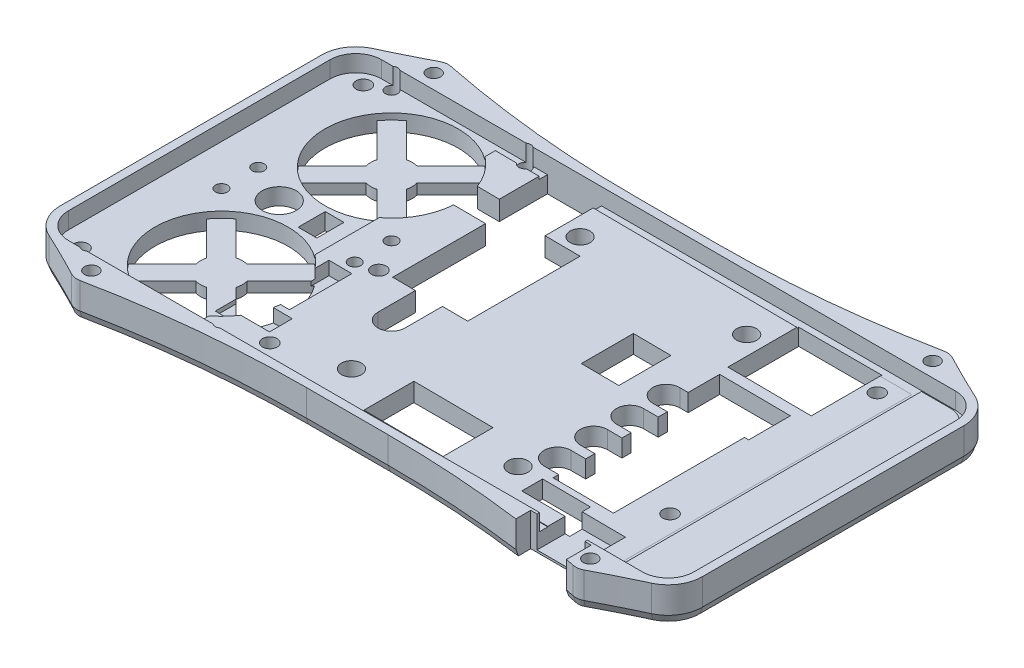
SolidWorks part; units mm, degrees
ref_plane "前视基准面" through (0, 0, 0) normal (0, 0, 1) x (1, 0, 0)
ref_plane "上视基准面" through (0, 0, 0) normal (0, 1, 0) x (1, 0, 0)
ref_plane "右视基准面" through (0, 0, 0) normal (1, 0, 0) x (0, 0, -1)
sketch "草图1" plane through (0, 0, 0) normal (0, 1, 0) x (1, 0, 0)
  line L0 (6, 0.2) -> (143.8, 0.2)
  line L1 (6, 0) -> (143.8, 0) construction
  line L2 (0, -6) -> (0, -68.8) construction
  line L3 (6, -74.8) -> (143.8, -74.8) construction
  line L4 (149.8, -6) -> (149.8, -68.8) construction
  line L5 (150, -6) -> (150, -68.8)
  line L6 (6, -75) -> (143.8, -75)
  line L7 (-0.2, -6) -> (-0.2, -68.8)
  arc A0 (143.8, 0) -> (149.8, -6) centre (143.8, -6) cw construction
  arc A1 (143.8, -74.8) -> (149.8, -68.8) centre (143.8, -68.8) ccw construction
  arc A2 (0, -68.8) -> (6, -74.8) centre (6, -68.8) ccw construction
  arc A3 (6, 0) -> (0, -6) centre (6, -6) ccw construction
  arc A4 (143.8, 0.2) -> (150, -6) centre (143.8, -6) cw
  arc A5 (143.8, -75) -> (150, -68.8) centre (143.8, -68.8) ccw
  arc A6 (-0.2, -68.8) -> (6, -75) centre (6, -68.8) ccw
  arc A7 (6, 0.2) -> (-0.2, -6) centre (6, -6) ccw
  point P7 (149.8, 0)
  point P12 (0, -74.8)
  point P15 (0, 0)
  dimension "D3" = 6
  dimension "D1" = 74.8
  dimension "D2" = 149.8
  dimension "D4" = 0.2
extrude "凸台-拉伸1" add sketch "草图1" along normal blind 4
sketch "草图2" plane through (0, 0, 0) normal (0, -1, 0) x (-1, 0, 0)
  line L0 (-122.6, -55.35) -> (-108.9, -55.35)
  line L1 (-122.6, -69.85) -> (-108.9, -69.85)
  line L2 (-122.6, -69.85) -> (-122.6, -63.95)
  line L3 (-122.6, -63.95) -> (-108.9, -63.95)
  line L4 (-108.9, -69.85) -> (-108.9, -63.95)
  line L5 (-135.3, -1.25) -> (-35.3, -1.25) construction
  line L6 (-135.3, -1.25) -> (-135.3, -73.55) construction
  line L7 (-135.3, -73.55) -> (-35.3, -73.55) construction
  line L8 (-35.3, -1.25) -> (-35.3, -73.55) construction
  line L9 (-108.9, -61.25) -> (-108.9, -55.35)
  line L10 (-122.6, -61.25) -> (-108.9, -61.25)
  line L11 (-122.6, -61.25) -> (-122.6, -55.35)
  line L12 (-122.6, -46.75) -> (-108.9, -46.75)
  line L13 (-108.9, -52.65) -> (-108.9, -46.75)
  line L14 (-122.6, -52.65) -> (-108.9, -52.65)
  line L15 (-122.6, -52.65) -> (-122.6, -46.75)
  line L16 (-122.6, -38.15) -> (-108.9, -38.15)
  line L17 (-108.9, -44.05) -> (-108.9, -38.15)
  line L18 (-122.6, -44.05) -> (-108.9, -44.05)
  line L19 (-122.6, -44.05) -> (-122.6, -38.15)
  line L20 (0, -6) -> (0, -68.8) construction
  line L21 (-35.3, -73.55) -> (-0.8, -73.55) construction
  line L22 (-120.25, -26.65) -> (-111.25, -26.65) construction
  line L23 (-120.25, -26.65) -> (-120.25, -33.15) construction
  line L24 (-120.25, -33.15) -> (-111.25, -33.15) construction
  line L25 (-111.25, -26.65) -> (-111.25, -33.15) construction
  line L26 (-85.8, -48.75) -> (-81.1, -48.75) construction
  line L27 (-85.8, -48.75) -> (-85.8, -58.15) construction
  line L28 (-85.8, -58.15) -> (-81.1, -58.15) construction
  line L29 (-81.1, -48.75) -> (-81.1, -58.15) construction
  line L30 (-71.5, -48.65) -> (-68.2, -48.65) construction
  line L31 (-71.5, -48.65) -> (-71.5, -57.55) construction
  line L32 (-71.5, -57.55) -> (-68.2, -57.55) construction
  line L33 (-68.2, -48.65) -> (-68.2, -57.55) construction
  line L34 (-43.1, -45.05) -> (-38.6, -45.05) construction
  line L35 (-43.1, -45.05) -> (-43.1, -59.05) construction
  line L36 (-43.1, -59.05) -> (-38.6, -59.05) construction
  line L37 (-38.6, -45.05) -> (-38.6, -59.05) construction
  line L38 (-45.3, -61.55) -> (-33.3, -61.55) construction
  line L39 (-45.3, -61.55) -> (-45.3, -66.05) construction
  line L40 (-45.3, -66.05) -> (-33.3, -66.05) construction
  line L41 (-33.3, -61.55) -> (-33.3, -66.05) construction
  line L42 (-0.8, -73.55) -> (-0.8, -1.25) construction
  line L43 (-0.8, -1.25) -> (-35.3, -1.25) construction
  line L44 (-149.8, -6) -> (-149.8, -68.8) construction
  line L45 (-30.8, -34.65) -> (-27.3, -34.65) construction
  line L46 (-30.8, -34.65) -> (-30.8, -40.15) construction
  line L47 (-30.8, -40.15) -> (-27.3, -40.15) construction
  line L48 (-27.3, -34.65) -> (-27.3, -40.15) construction
  line L49 (-120.75, -33.65) -> (-110.75, -33.65)
  line L50 (-110.75, -26.15) -> (-110.75, -33.65)
  line L51 (-120.75, -26.15) -> (-110.75, -26.15)
  line L52 (-120.75, -26.15) -> (-120.75, -33.65)
  line L53 (-86.3, -48.25) -> (-86.3, -58.65)
  line L54 (-86.3, -58.65) -> (-80.6, -58.65)
  line L55 (-80.6, -48.25) -> (-80.6, -58.65)
  line L56 (-86.3, -48.25) -> (-80.6, -48.25)
  line L57 (-72, -48.15) -> (-72, -58.05)
  line L58 (-72, -58.05) -> (-67.7, -58.05)
  line L59 (-67.7, -48.15) -> (-67.7, -58.05)
  line L60 (-72, -48.15) -> (-67.7, -48.15)
  line L61 (-31.3, -34.15) -> (-31.3, -40.65)
  line L62 (-31.3, -40.65) -> (-26.8, -40.65)
  line L63 (-26.8, -34.15) -> (-26.8, -40.65)
  line L64 (-31.3, -34.15) -> (-26.8, -34.15)
  line L65 (-43.6, -44.55) -> (-43.6, -59.55)
  line L66 (-43.6, -59.55) -> (-38.1, -59.55)
  line L67 (-38.1, -44.55) -> (-38.1, -59.55)
  line L68 (-43.6, -44.55) -> (-38.1, -44.55)
  line L69 (-45.8, -61.05) -> (-45.8, -66.55)
  line L70 (-45.8, -66.55) -> (-32.8, -66.55)
  line L71 (-32.8, -61.05) -> (-32.8, -66.55)
  line L72 (-45.8, -61.05) -> (-32.8, -61.05)
  circle A0 centre (-103.2, -9.35) radius 2 construction
  circle A1 centre (-103.2, -64.25) radius 2 construction
  circle A2 centre (-63.2, -64.25) radius 2 construction
  circle A3 centre (-63.2, -9.35) radius 2 construction
  circle A4 centre (-130.8, -5.6) radius 1.25 construction
  circle A5 centre (-131.1, -55.65) radius 1.25 construction
  circle A6 centre (-47.7, -4.85) radius 1.25 construction
  circle A7 centre (-48.1, -68.75) radius 1.25 construction
  circle A8 centre (-22.8, -70.3) radius 1.25 construction
  circle A9 centre (-5.05, -71.05) radius 1.25 construction
  circle A10 centre (-5.05, -3.25) radius 1.25 construction
  circle A11 centre (-19, -37.4) radius 3.6 construction
  circle A12 centre (-103.2, -9.35) radius 2.4
  circle A13 centre (-63.2, -9.35) radius 2.4
  circle A14 centre (-63.2, -64.25) radius 2.4
  circle A15 centre (-103.2, -64.25) radius 2.4
  circle A16 centre (-19, -37.4) radius 4.1
  circle A17 centre (-130.8, -5.6) radius 1.75
  circle A18 centre (-131.1, -55.65) radius 1.75
  circle A19 centre (-48.1, -68.75) radius 1.75
  circle A20 centre (-22.8, -70.3) radius 1.75
  circle A21 centre (-5.05, -71.05) radius 1.75
  circle A22 centre (-5.05, -3.25) radius 1.75
  circle A23 centre (-47.7, -4.85) radius 1.75
  circle A24 centre (-46.11, -40.57) radius 1.25 construction
  circle A25 centre (-46.11, -40.57) radius 1.75
  point P22 (0, -37.4)
  point P23 (-135.3, -37.4)
  point P28 (-115.75, -33.15)
  point P29 (-115.75, -38.15)
  point P30 (-111.25, -29.9)
  point P31 (-108.9, -41.1)
  point P79 (-0.8, -37.4)
  point P81 (-27.3, -37.4)
  dimension "D21" = 4
  dimension "D34" = 2.5
  dimension "D53" = 7.2
  dimension "D1" = 13.7
  dimension "D2" = 5.9
  dimension "D3" = 72.3
  dimension "D4" = 3.7
  dimension "D5" = 12.7
  dimension "D7" = 14.5
  dimension "D8" = 100
  dimension "D9" = 2.7
  dimension "D10" = 9
  dimension "D11" = 6.5
  dimension "D12" = 11.2
  dimension "D13" = 15.4
  dimension "D14" = 9.4
  dimension "D15" = 4.7
  dimension "D16" = 23.1
  dimension "D17" = 3.3
  dimension "D18" = 8.9
  dimension "D19" = 16
  dimension "D20" = 37.4
  dimension "D22" = 8.1
  dimension "D23" = 32.1
  dimension "D24" = 40
  dimension "D25" = 9.3
  dimension "D26" = 14
  dimension "D27" = 4.5
  dimension "D28" = 12
  dimension "D29" = 4.5
  dimension "D30" = 3.3
  dimension "D31" = 2
  dimension "D32" = 7.5
  dimension "D33" = 14.5
  dimension "D35" = 34.5
  dimension "D36" = 2
  dimension "D37" = 4.25
  dimension "D38" = 2.5
  dimension "D39" = 3.25
  dimension "D40" = 22
  dimension "D41" = 4.8
  dimension "D42" = 12.8
  dimension "D43" = 3.6
  dimension "D44" = 12.4
  dimension "D45" = 4.35
  dimension "D46" = 4.5
  dimension "D47" = 4.2
  dimension "D48" = 17.9
  dimension "D49" = 18.2
  dimension "D50" = 3.5
  dimension "D51" = 5.5
  dimension "D52" = 8.3
  dimension "D58" = 28.18
  dimension "D59" = 1.99
  dimension "D54" = 0.4
  dimension "D55" = 0.5
  dimension "D56" = 0.5
  dimension "D57" = 0.5
  dimension "D6" = 4
sketch "草图7" plane through (0, 0, -0.2) normal (0, 0, -1) x (-1, 0, 0)
  line L0 (-135.3, 4) -> (-35.3, 4.75)
  line L2 (-35.3, 4.75) -> (-35.3, 4)
  line L4 (-35.3, 4) -> (-135.3, 4)
  line L6 (-143.8, 4) -> (-6, 4) construction
  dimension "D1" = 0.75
extrude "凸台-拉伸11" add sketch "草图7" against normal offset from surface (71.2 mm away) 2 from offset 2 up to face at (74.9, 2, 75) offset against normal yes
extrude "切除-拉伸1" cut sketch "草图2" against normal blind 10 contours A12 | A13 | A14 | A15
sketch "草图3" plane through (0, 0, 0) normal (0, 1, 0) x (1, 0, 0)
  line L0 (136.8, -1) -> (136.8, -73.8)
  line L1 (143.8, 0) -> (135.8, 0) construction
  line L2 (149.8, -6) -> (149.8, -68.8) construction
  line L3 (143.8, -74.8) -> (135.8, -74.8) construction
  line L4 (135.8, 0) -> (135.8, -74.8) construction
  line L5 (6, -74.8) -> (143.8, -74.8) construction
  line L6 (135.3, -1.25) -> (135.3, -73.55) construction
  line L7 (143.8, -73.8) -> (136.8, -73.8)
  line L8 (148.8, -6) -> (148.8, -68.8)
  line L9 (143.8, -1) -> (136.8, -1)
  arc A0 (143.8, 0) -> (149.8, -6) centre (143.8, -6) cw construction
  arc A1 (149.8, -68.8) -> (143.8, -74.8) centre (143.8, -68.8) cw construction
  arc A2 (148.8, -68.8) -> (143.8, -73.8) centre (143.8, -68.8) cw
  arc A3 (143.8, -1) -> (148.8, -6) centre (143.8, -6) cw
  point P17 (149.8, 0)
  dimension "D1" = 6
  dimension "D2" = 0.5
extrude "凸台-拉伸9" add sketch "草图3" along normal offset from surface (5 mm away) 1 up to face at (85.3, 4, 37.4) offset beyond the face yes
sketch "草图4" plane through (0, 0, 0) normal (0, 1, 0) x (1, 0, 0)
  line L0 (125.2, -20.85) -> (108.2, -20.85)
  line L1 (108.2, -30.85) -> (109.7, -30.85)
  line L2 (109.7, -30.85) -> (109.7, -62.35)
  line L3 (108.7, -68.85) -> (108.7, -62.35)
  line L4 (49.2, -40.35) -> (49.2, -13.35)
  line L5 (108.2, -30.85) -> (108.2, -20.85)
  line L6 (108.7, -68.85) -> (120.2, -68.85)
  line L7 (108.2, -30.85) -> (125.2, -30.85) construction
  line L8 (109.7, -62.35) -> (124.2, -62.35)
  line L9 (80.466, -18.85) -> (96.6871, -18.85) construction
  line L10 (107.2, 11.628) -> (107.2, 24.7853) construction
  line L11 (49.2, -13.35) -> (67.2, -13.35)
  line L12 (125.2, -30.85) -> (124.2, -30.85)
  line L13 (124.2, -30.85) -> (124.2, -62.35)
  line L14 (124.2, -62.35) -> (120.2, -62.35)
  line L15 (120.2, -62.35) -> (120.2, -68.85)
  line L16 (67.2, -13.35) -> (67.2, -40.35)
  line L17 (67.2, -40.35) -> (49.2, -40.35)
  line L18 (63.2, -9.35) -> (46.0308, -9.35) construction
  line L19 (106.2, -55.55) -> (106.2, -28.85) construction
  line L20 (108.7, -63.85) -> (120.2, -63.85)
  line L21 (125.2, -20.85) -> (125.2, -30.85)
  line L22 (106.2, -28.4) -> (108.2, -28.4)
  line L23 (106.2, -34.9) -> (109.7, -34.9)
  line L24 (106.2, -37.1) -> (109.7, -37.1)
  line L25 (109.7, -37.1) -> (109.7, -43.6)
  line L26 (109.7, -43.6) -> (106.2, -43.6)
  line L27 (106.2, -45.8) -> (109.7, -45.8)
  line L28 (106.2, -52.3) -> (109.7, -52.3)
  line L29 (106.2, -54.5) -> (109.7, -54.5)
  line L30 (106.2, -61) -> (109.7, -61)
  line L31 (54.65, -49.35) -> (54.65, -40.35)
  line L32 (61.15, -49.35) -> (61.15, -40.35)
  line L33 (89.5, -35.35) -> (89.5, -22.85)
  line L34 (89.5, -22.85) -> (98.5, -22.85)
  line L35 (98.5, -22.85) -> (98.5, -35.35)
  line L36 (98.5, -35.35) -> (89.5, -35.35)
  line L37 (58.8, -1.85) -> (58.8, -13.85)
  line L38 (58.8, -13.85) -> (45.8, -13.85)
  line L39 (107.7, -18.35) -> (107.7, -1.35)
  line L40 (107.7, -1.35) -> (127.7, -1.35)
  line L41 (127.7, -1.35) -> (127.7, -18.35)
  line L42 (127.7, -18.35) -> (107.7, -18.35)
  line L43 (92.2, -59.25) -> (92.2, -71.25)
  line L44 (92.2, -71.25) -> (73.2, -71.25)
  line L45 (73.2, -71.25) -> (73.2, -59.25)
  line L46 (73.2, -59.25) -> (92.2, -59.25)
  line L47 (45.8, -13.85) -> (45.8, -1.85)
  line L48 (45.8, -1.85) -> (58.8, -1.85)
  line L49 (45.8, -11.35) -> (39.8, -11.35)
  line L50 (39.8, -11.35) -> (39.8, -18.05)
  line L51 (39.8, -18.05) -> (45.8, -18.05)
  line L52 (45.8, -18.05) -> (45.8, -11.35)
  line L53 (45.8, -18.05) -> (49.2, -18.05)
  line L54 (45.8, -1.85) -> (45.8, 0.2)
  line L55 (143.8, 0.2) -> (6, 0.2) construction
  line L56 (45.8, 0.2) -> (58.8, 0.2)
  line L57 (58.8, 0.2) -> (58.8, -1.85)
  circle A0 centre (103.2, -9.35) radius 2.4 construction
  circle A1 centre (103.2, -64.25) radius 2.4 construction
  circle A2 centre (103.2, -64.25) radius 2.4
  circle A3 centre (63.2, -64.25) radius 2.4 construction
  circle A4 centre (63.2, -64.25) radius 2.4
  circle A5 centre (103.2, -9.35) radius 2.4 construction
  circle A6 centre (106.2, -31.65) radius 3.25
  circle A7 centre (106.2, -40.35) radius 3.25
  circle A8 centre (106.2, -49.05) radius 3.25
  circle A9 centre (106.2, -57.75) radius 3.25
  circle A10 centre (63.2, -9.35) radius 2.4 construction
  circle A11 centre (63.2, -9.35) radius 2.4 construction
  circle A12 centre (57.9, -49.35) radius 3.25
  point P30 (67.2, -26.85)
  dimension "D7" = 9.5
  dimension "D30" = 4.5
  dimension "D40" = 6.5
  dimension "D18" = 6.5
  dimension "D21" = 4.5
  dimension "D4" = 11.5
  dimension "D5" = 48
  dimension "D6" = 10
  dimension "D8" = 4
  dimension "D9" = 5
  dimension "D10" = 5
  dimension "D11" = 17
  dimension "D12" = 6.5
  dimension "D13" = 1
  dimension "D14" = 14
  dimension "D15" = 18
  dimension "D16" = 4
  dimension "D17" = 27
  dimension "D19" = 40
  dimension "D20" = 5.3
  dimension "D22" = 4.4
  dimension "D23" = 13
  dimension "D24" = 1.5
  dimension "D25" = 12.5
  dimension "D26" = 5.5
  dimension "D27" = 9
  dimension "D28" = 8.7
  dimension "D29" = 12
  dimension "D31" = 20
  dimension "D32" = 9
  dimension "D33" = 17
  dimension "D34" = 11
  dimension "D35" = 19
  dimension "D36" = 12
  dimension "D37" = 7
  dimension "D38" = 11.5
  dimension "D39" = 22.3
  dimension "D41" = 3
  dimension "D43" = 13.5
  dimension "D44" = 4.7
  dimension "D45" = 6
  dimension "D46" = 2.5
  dimension "D47" = 6.7
  dimension "D42" = 4
extrude "拉伸-薄壁1" add sketch "草图1<2>" along normal blind 8 thin thin type one direction wall 2
sketch "草图1<2>" plane through (0, 0, 0) normal (0, 1, 0) x (1, 0, 0) same geometry as "草图1"
extrude "切除-拉伸2" cut sketch "草图4" along normal through all contours L20 L3 L6 L15 | A9 L30 L2 L29 | A8 L28 L2 L27 | A7 L26 L2 L24 | A6 L23 L2 L1 | A6 L5 L22 | A12 L17 L31 | A12 L32 L17 | L52 L53 L4 L38 | L57 L56 L54 L48 | L41 L42 L39 L40 | L8 L2 L1 L5 L0 L21 L12 L13 | A6 | A7 | A8 | A9 | L46 L43 L44 L45 | L35 L36 L33 L34 | L4 L11 L16 L17 | A12 | L47 L48 L37 L38 | L50 L51 L52 L49 region at (114.45, 0, 66.35) region at (107.7112, 0, 28.6021) region at (108.9903, 0, 33.7511) region at (109.6262, 0, 40.35) region at (107.95, 0, 60.9262) region at (109.6262, 0, 49.05) region at (47.5, 0, 15.95) region at (57.9, 0, 43.6145) region at (52.3, 0, 0.825)
extrude "切除-拉伸3" cut sketch "草图2<11>" against normal through all contours L61 L62 L63 L64 | A16
sketch "草图2<11>" plane through (0, 0, 0) normal (0, -1, 0) x (-1, 0, 0) same geometry as "草图2"
extrude "切除-拉伸4" cut sketch "草图2<13>" against normal through all contours A17 | A18 | A19 | A23 | A22 | A21 | A25
sketch "草图2<13>" plane through (0, 0, 0) normal (0, -1, 0) x (-1, 0, 0) same geometry as "草图2"
extrude "切除-拉伸5" cut sketch "草图2<14>" against normal through all from offset 1.5 contours L67 L66 L65 L68 | L71 L70 L69 L72 offset against normal yes
sketch "草图2<14>" plane through (0, 0, 0) normal (0, -1, 0) x (-1, 0, 0) same geometry as "草图2"
sketch "草图5" plane through (0, 0, 0) normal (0, -1, 0) x (-1, 0, 0)
  text T0 "<b>M3*6</b>" font "@Adobe 黑体 Std R" height 7
  text T1 "<b>M3*6</b>" font "@Adobe 黑体 Std R" height 7
  text T2 "<b>M3*6</b>" font "@Adobe 黑体 Std R" height 7
  text T3 "<b>M3*6</b>" font "@Adobe 黑体 Std R" height 7
extrude "切除-拉伸6" [suppressed] cut sketch "草图5" against normal blind 0.6
sketch "草图6" plane through (0, 0, 0) normal (0, 1, 0) x (1, 0, 0)
  line L1 (0, -6) -> (0, -68.8) construction
  line L2 (149.8, -6) -> (149.8, -68.8) construction
  line L4 (6, 0.2) -> (143.8, 0.2) construction
  line L5 (6, -75) -> (143.8, -75) construction
  circle A0 centre (15, 3.7) radius 1.5 construction
  circle A1 centre (15, -78.5) radius 1.5 construction
  circle A2 centre (134.8, 3.7) radius 1.5 construction
  circle A3 centre (134.8, -78.5) radius 1.5 construction
  circle A4 centre (15, 3.7) radius 3.5
  circle A5 centre (15, -78.5) radius 3.5
  circle A6 centre (134.8, 3.7) radius 3.5
  circle A7 centre (134.8, -78.5) radius 3.5
  circle A8 centre (15, 3.7) radius 1.65
  circle A9 centre (134.8, 3.7) radius 1.65
  circle A10 centre (134.8, -78.5) radius 1.65
  circle A11 centre (15, -78.5) radius 1.65
  dimension "D1" = 3
  dimension "D3" = 0.15
  dimension "D4" = 15
  dimension "D5" = 15
  dimension "D2" = 2
extrude "凸台-拉伸10" add sketch "草图6" along normal up to surface (8 mm away) up to face at (74.9, 8, 37.4)
extrude "切除-拉伸9" cut sketch "草图6<2>" along normal through all contours A8 | A9 | A10 | A11
sketch "草图6<2>" plane through (0, 0, 0) normal (0, 1, 0) x (1, 0, 0) same geometry as "草图6"
fillet "圆角1" radius 250 8 edges at (18.1623, 4, 77) (11.8377, 4, 77) (131.6377, 4, 77) (137.9623, 4, 77) (137.9623, 4, -2.2) (131.6377, 4, -2.2) (11.8377, 4, -2.2) (18.1623, 4, -2.2)
chamfer "倒角1" distance 0.6 angle 70 20 edges at (40.2731, 0, 78.2358) (14.5029, 0, 81.9645) (74.9, 0, 77) (7.988, 0, 78.8506) (109.5269, 0, 78.2358) (-0.9143, 0, 73.2083) (135.2971, 0, 81.9645) (-2.2, 0, 37.4) (141.812, 0, 78.8506) (-0.9143, 0, 1.5917) (150.7143, 0, 73.2083) (7.988, 0, -4.0506) (152, 0, 37.4) (14.5029, 0, -7.1645) (150.7143, 0, 1.5917) (40.2731, 0, -3.4358) (141.812, 0, -4.0506) (74.9, 0, -2.2) (135.2971, 0, -7.1645) (109.5269, 0, -3.4358) first distance on face at (134.8, 0, 80.15)
sketch "草图8" plane through (0, 0, 0) normal (0, -1, 0) x (1, 0, 0)
  line L0 (9.5525, 32.9807) -> (9.5525, 0.9807) construction
  line L1 (9.5525, 0.9807) -> (41.5525, 0.9807) construction
  line L2 (41.5525, 0.9807) -> (41.5525, 32.9807) construction
  line L3 (41.5525, 32.9807) -> (9.5525, 32.9807) construction
  line L4 (31.3, 37.4) -> (26.8, 37.4) construction
  line L7 (41.5525, 41.8193) -> (9.5525, 41.8193) construction
  line L8 (41.5525, 73.8193) -> (41.5525, 41.8193) construction
  line L9 (9.5525, 73.8193) -> (41.5525, 73.8193) construction
  line L10 (9.5525, 41.8193) -> (9.5525, 73.8193) construction
  circle A0 centre (41.5525, 0.9807) radius 1.45
  circle A1 centre (41.5525, 32.9807) radius 1.45
  circle A2 centre (9.5525, 32.9807) radius 1.45
  circle A3 centre (9.5525, 0.9807) radius 1.45
  circle A4 centre (9.5525, 73.8193) radius 1.45
  circle A5 centre (9.5525, 41.8193) radius 1.45
  circle A6 centre (41.5525, 41.8193) radius 1.45
  circle A7 centre (41.5525, 73.8193) radius 1.45
  point P4 (9.5525, 16.9807)
  dimension "D3" = 2.9
  dimension "D4" = 2.9
  dimension "D5" = 2.9
  dimension "D6" = 2.9
  dimension "D1" = 32
  dimension "D2" = 32
extrude "切除-拉伸10" cut sketch "草图8" against normal through all
sketch "草图9" plane through (0, 0, 0) normal (0, -1, 0) x (1, 0, 0)
  line L0 (9.5525, 32.9807) -> (41.5525, 32.9807) construction
  line L1 (41.5525, 32.9807) -> (41.5525, 0.9807) construction
  line L2 (41.5525, 0.9807) -> (9.5525, 0.9807) construction
  line L3 (9.5525, 0.9807) -> (9.5525, 32.9807) construction
  line L4 (9.5525, 32.9807) -> (41.5525, 0.9807) construction
  line L5 (41.5525, 32.9807) -> (9.5525, 0.9807) construction
  line L6 (13.088, 32.9807) -> (41.5525, 4.5163)
  line L7 (41.5525, 4.5163) -> (38.017, 0.9807)
  line L8 (38.017, 0.9807) -> (9.5525, 29.4452)
  line L9 (9.5525, 29.4452) -> (13.088, 32.9807)
  line L10 (38.017, 32.9807) -> (9.5525, 4.5163)
  line L11 (9.5525, 4.5163) -> (13.088, 0.9807)
  line L12 (13.088, 0.9807) -> (41.5525, 29.4452)
  line L13 (41.5525, 29.4452) -> (38.017, 32.9807)
  line L14 (9.5525, 0.9807) -> (41.5525, 0.9807) construction
  line L15 (31.3, 37.4) -> (26.8, 37.4) construction
  line L18 (9.5525, 73.8193) -> (41.5525, 73.8193) construction
  line L19 (9.5525, 41.8193) -> (41.5525, 73.8193) construction
  line L20 (9.5525, 73.8193) -> (9.5525, 41.8193) construction
  line L21 (41.5525, 73.8193) -> (9.5525, 73.8193) construction
  line L22 (41.5525, 41.8193) -> (41.5525, 73.8193) construction
  line L23 (9.5525, 41.8193) -> (41.5525, 41.8193) construction
  line L24 (41.5525, 45.3548) -> (38.017, 41.8193)
  line L25 (13.088, 73.8193) -> (41.5525, 45.3548)
  line L26 (9.5525, 70.2837) -> (13.088, 73.8193)
  line L27 (38.017, 41.8193) -> (9.5525, 70.2837)
  line L28 (9.5525, 45.3548) -> (13.088, 41.8193)
  line L29 (38.017, 73.8193) -> (9.5525, 45.3548)
  line L30 (41.5525, 70.2837) -> (38.017, 73.8193)
  line L31 (13.088, 41.8193) -> (41.5525, 70.2837)
  line L32 (41.5525, 41.8193) -> (9.5525, 73.8193) construction
  circle A0 centre (25.5525, 16.9807) radius 16
  circle A1 centre (25.5525, 16.9807) radius 5
  circle A2 centre (25.5525, 57.8193) radius 5
  circle A3 centre (25.5525, 57.8193) radius 16
  dimension "D2" = 10
  dimension "D4" = 5
extrude "切除-拉伸11" cut sketch "草图9" against normal blind 10 contours A1 L10 A0 L6 | A1 L6 A0 L12 | A1 L12 A0 L8 | A1 L8 A0 L10 | A3 L29 A2 L27 | A3 L25 A2 L29 | A3 L31 A2 L25 | A3 L27 A2 L31 region at (25.5525, 0, 28.2322) region at (14.301, 0, 16.9807) region at (36.804, 0, 16.9807) region at (25.5525, 0, 5.7292) region at (36.804, 0, 57.8193) region at (25.5525, 0, 46.5678) region at (14.301, 0, 57.8193) region at (25.5525, 0, 69.0708)
sketch "草图10" plane through (0, 4, 0) normal (0, 1, 0) x (1, 0, 0)
  circle A0 centre (25.5525, -16.9807) radius 16
  circle A1 centre (25.5525, -57.8193) radius 16
  dimension "D1" = 32
  dimension "D2" = 32
extrude "切除-拉伸12" cut sketch "草图10" against normal mid plane 3
sketch "草图11" plane through (0, 8, 0) normal (0, 1, 0) x (1, 0, 0)
  line L0 (119.1, -85.85) -> (119.1, -65.85)
  line L1 (119.1, -65.85) -> (130.6, -65.85)
  line L2 (130.6, -65.85) -> (130.6, -85.85)
  line L3 (130.6, -85.85) -> (119.1, -85.85)
  line L4 (120.2, -63.85) -> (108.7, -63.85) construction
  circle A0 centre (131.1, -55.65) radius 1.75 construction
  circle A1 centre (131.1, -55.65) radius 1.75 construction
  dimension "D1" = 11.5
  dimension "D2" = 0.5
  dimension "D3" = 2
  dimension "D4" = 20
extrude "切除-拉伸13" cut sketch "草图11" against normal blind 4.5 from surface starting at face at (143.4785, 5, 37.4)
sketch "草图12" plane through (0, 8, 0) normal (0, 1, 0) x (1, 0, 0)
  line L0 (117.6, -75.6) -> (117.6, -88.4406)
  line L1 (117.6, -88.4406) -> (132.1, -88.4406)
  line L2 (132.1, -88.4406) -> (132.1, -75.6)
  line L3 (132.1, -75.6) -> (117.6, -75.6)
  line L4 (42.3942, -75) -> (143.8, -75) construction
  line L5 (119.1, -73) -> (119.1, -75) construction
  line L6 (130.6, -75) -> (130.6, -73) construction
  dimension "D1" = 0.6
  dimension "D2" = 1.5
  dimension "D3" = 1.5
extrude "切除-拉伸14" cut sketch "草图12" against normal through all
sketch "草图13" plane through (0, 0, 75.6) normal (0, 0, 1) x (1, 0, 0)
  line L0 (130.6, 5) -> (130.6, 8)
  line L1 (132.1, 8) -> (117.6, 8) construction
  line L2 (130.6, 8) -> (119.1, 8)
  line L3 (119.1, 8) -> (119.1, 5)
  line L4 (119.1, 5) -> (130.6, 5)
extrude "切除-拉伸15" cut sketch "草图13" against normal up to next
equation "\"D1@草图3\"=\"D3@草图1\""
